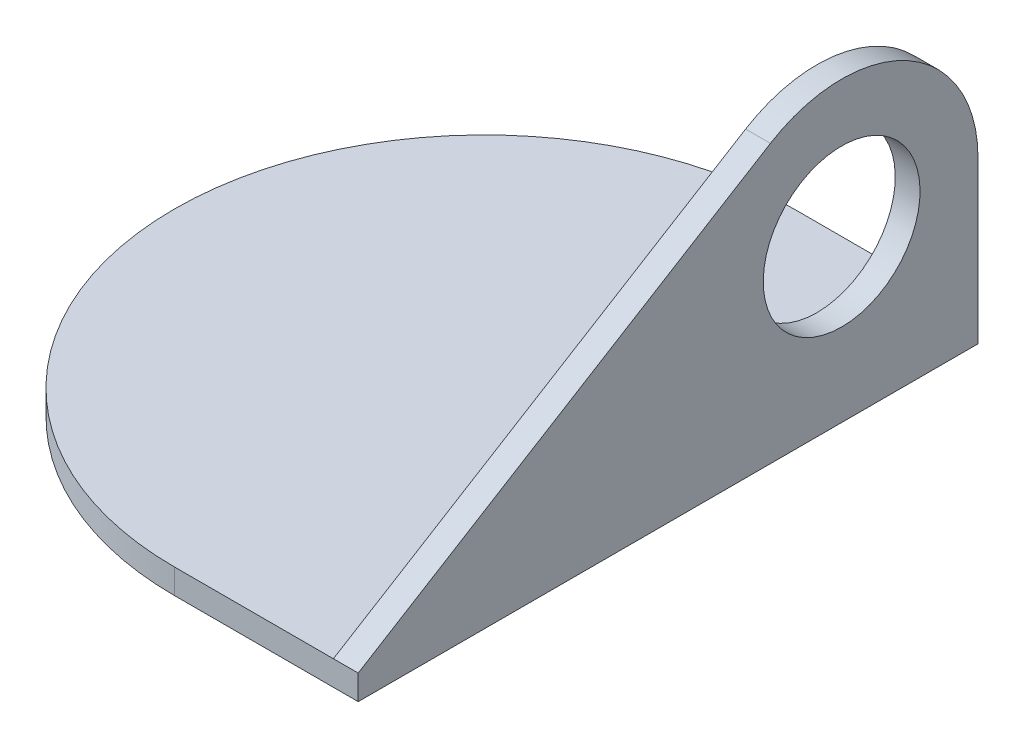
SolidWorks part; units mm, degrees
ref_plane "Front Plane" through (0, 0, 0) normal (0, 0, 1) x (1, 0, 0)
ref_plane "Top Plane" through (0, 0, 0) normal (0, 1, 0) x (1, 0, 0)
ref_plane "Right Plane" through (0, 0, 0) normal (1, 0, 0) x (0, 0, -1)
sketch "Sketch2" plane through (0, 0, 0) normal (0, 0, 1) x (1, 0, 0)
  line L0 (0, 8.1269) -> (0, -11.1542) construction
  line L1 (-11.5687, 0) -> (13.6229, 0) construction
  line L2 (0, 0) -> (-25.4, 0)
  line L3 (0, 0) -> (0, 25.4)
  dimension "D1" = 25.4
  dimension "D2" = 25.4
extrude "Extrude-Thin1" add sketch "Sketch2" along normal mid plane 25.4 thin thin type one direction wall 1.016
sketch "Sketch3" plane through (0, 0, 0) normal (-1, 0, 0) x (0, 0, 1)
  line L0 (12.7, 0) -> (-12.7, 0) construction
  line L5 (-12.7, 0) -> (-12.7, 25.4) construction
  line L6 (-7.112, 27.0358) -> (-7.112, -10.078) construction
  line L7 (-20.3076, 5.588) -> (17.3462, 5.588) construction
  circle A0 centre (-7.112, 5.588) radius 3.2131
  dimension "D2" = 6.4262
  dimension "D1" = 5.588
  dimension "D3" = 5.588
extrude "Cut-Extrude1" cut sketch "Sketch3" against normal through all
sketch "Sketch4" plane through (0, 0, 0) normal (-1, 0, 0) x (0, 0, 1)
  line L0 (-12.7, 0) -> (-12.7, 25.4) construction
  line L1 (12.7, 0) -> (-4.1921, 10.3524)
  line L5 (-12.7, 5.588) -> (-12.7, 25.4)
  line L6 (-12.7, 25.4) -> (12.7, 25.4)
  line L7 (12.7, 25.4) -> (12.7, 0)
  arc A0 (-4.1921, 10.3524) -> (-12.7, 5.588) centre (-7.112, 5.588) ccw
extrude "Cut-Extrude3" cut sketch "Sketch4" against normal through all
sketch "Sketch6" plane through (0, 0, 0) normal (0, 1, 0) x (1, 0, 0)
  line L0 (0, 12.7) -> (-11.43, 12.7)
  line L2 (-11.43, 12.7) -> (-25.4, 0)
  line L3 (-25.4, -12.7) -> (-25.4, 12.7) construction
  line L4 (-25.4, 0) -> (-11.43, -12.7)
  line L6 (-11.43, -12.7) -> (0, -12.7)
  line L7 (-25.4, 12.7) -> (0, 12.7) construction
  line L8 (-25.4, -12.7) -> (0, -12.7) construction
  point P3 (-12.7, 12.7)
  point P4 (-13.3611, 12.7)
  point P5 (-12.7, 12.7)
  point P10 (-10.2992, -12.7)
  point P16 (0, 0)
  point P18 (-11.43, -12.7)
  point P19 (-25.4, 0)
  line M4 (0, 12.7) -> (-25.4, 12.7)
  line M5 (-25.4, 12.7) -> (-25.4, -12.7)
  line M6 (-25.4, -12.7) -> (0, -12.7)
  dimension "D1" = 11.43
extrude "Cut-Extrude4" cut sketch "Sketch6" against normal through all both and the other way through all contours L2 M4 M5 | L4 M5 M6 region at (-20.7433, 0, 8.4667) region at (-20.7433, 0, -8.4667)
fillet "Fillet2" radius 12.7 3 edges at (-11.43, -0.508, 12.7) (-11.43, -0.508, -12.7) (-25.4, -0.508, 0)
